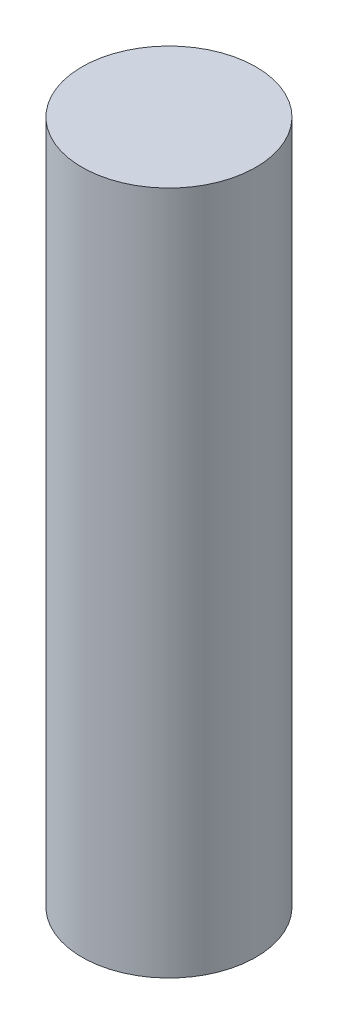
SolidWorks part; units mm, degrees
ref_plane "Front Plane" through (0, 0, 0) normal (0, 0, 1) x (1, 0, 0)
ref_plane "Top Plane" through (0, 0, 0) normal (0, 1, 0) x (1, 0, 0)
ref_plane "Right Plane" through (0, 0, 0) normal (1, 0, 0) x (0, 0, -1)
sketch "Sketch1" plane through (0, 0, 0) normal (0, 1, 0) x (1, 0, 0)
  circle A0 centre (0, 0) radius 14.5
extrude "Boss-Extrude1" add sketch "Sketch1" along normal mid plane 114 contours A0
ref_axis "Axis1" through (0, 57, 0) along (0, -1, 0)
